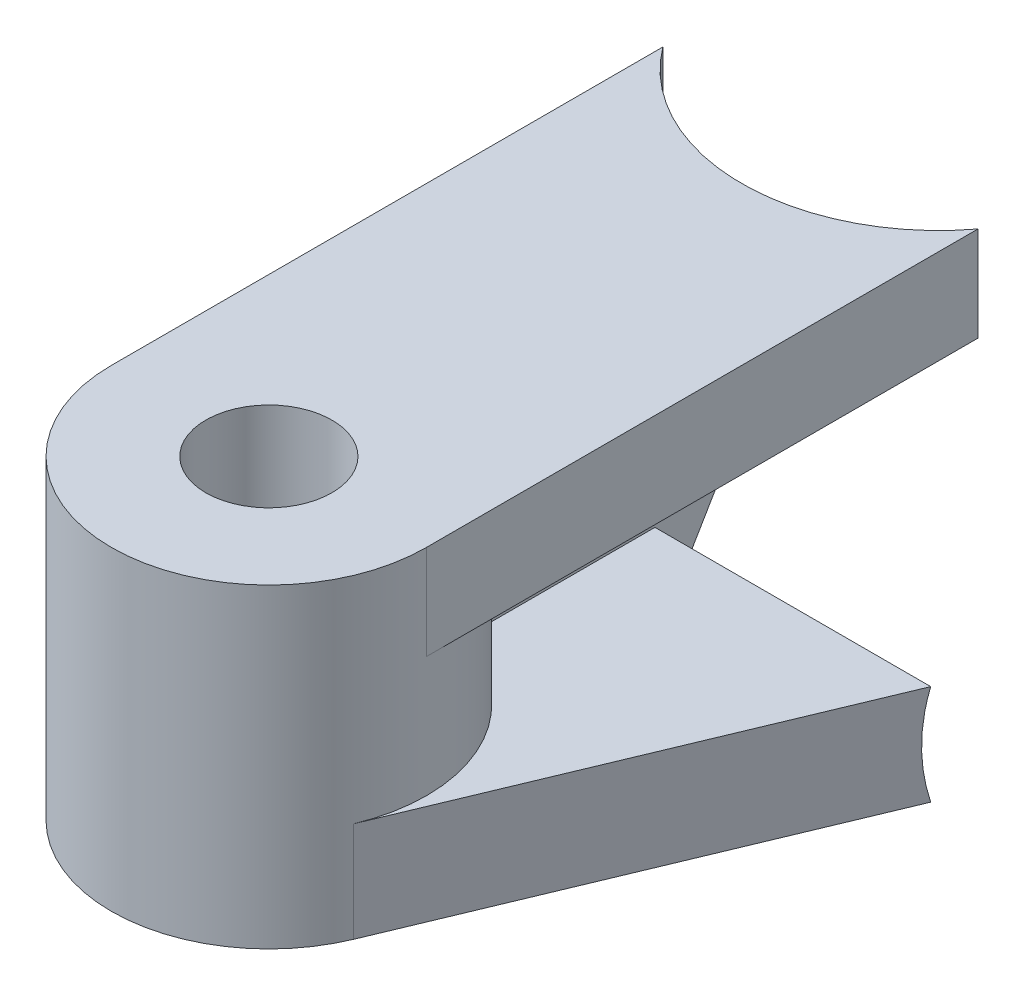
SolidWorks part; units mm, degrees
note: The reader was unsure of these and kept them because the rebuilt part matched: shared geometry of "Sketch1<3>".
ref_plane "Front Plane" through (0, 0, 0) normal (0, 0, 1) x (1, 0, 0)
ref_plane "Top Plane" through (0, 0, 0) normal (0, 1, 0) x (1, 0, 0)
ref_plane "Right Plane" through (0, 0, 0) normal (1, 0, 0) x (0, 0, -1)
sketch "Sketch1" plane through (0, 0, 0) normal (0, 1, 0) x (1, 0, 0)
  line L0 (0, 0) -> (40, 0)
  line L4 (0, 0) -> (10.7692, -25.8462)
  line L5 (29.2308, -25.8462) -> (40, 0)
  line L6 (20, 0) -> (20, -17.1488) construction
  line L7 (10.7692, -25.8462) -> (29.2308, -25.8462) construction
  circle A0 centre (20, -22) radius 4
  circle A1 centre (20, -22) radius 10
  point P7 (10.7978, -25.9141)
  dimension "D2" = 20
  dimension "D3" = 8
  dimension "D1" = 40
  dimension "D4" = 22
extrude "Boss-Extrude1" add sketch "Sketch1" along normal blind 6.35 contours A1 L5 L0 L4
extrude "Boss-Extrude2" add sketch "Sketch1<3>" along normal blind 20 contours A1 A0
sketch "Sketch1<3>" plane through (0, 0, 0) normal (0, 1, 0) x (1, 0, 0) same geometry as "Sketch1"
ref_plane "Plane1" through (0, 10, 0) normal (0, 1, 0) x (1, 0, 0)
sketch "Sketch2" plane through (0, 0, 0) normal (1, 0, 0) x (0, 0, -1)
  line L0 (0, 3.175) -> (21.8325, 3.175) construction
  line L1 (0, 6.35) -> (0, 0) construction
  circle A0 centre (12.0901, 3.175) radius 12.5
  dimension "D1" = 25
extrude "Cut-Extrude1" cut sketch "Sketch2" along normal through all
sketch "Sketch3" plane through (0, 20, 0) normal (0, 1, 0) x (1, 0, 0)
  line L0 (20, 13) -> (20, 20.5) construction
  line L2 (10, -22) -> (10, 13)
  line L3 (10, 13) -> (30, 13)
  line L4 (30, -22) -> (30, 13)
  line L6 (20, 20.5) -> (20, -18)
  circle A1 centre (20, -22) radius 4
  circle A2 centre (20, 20.5) radius 12.5
  circle A3 centre (20, -22) radius 10 construction
  arc A4 (29.2308, -25.8462) -> (10.7692, -25.8462) centre (20, -22) ccw construction
  point P9 (10.0056, -22.3357)
  point P16 (10, -22)
  dimension "D1" = 25
  dimension "D2" = 35
extrude "Boss-Extrude3" add sketch "Sketch3" against normal blind 6
sketch "Sketch4" plane through (0, 14, 0) normal (0, -1, 0) x (1, 0, 0)
  line L0 (20, -8) -> (20, 12) construction
  line L1 (17.5, -8.2526) -> (17.5, 12.3175)
  line L2 (22.5, -8.2526) -> (22.5, 12.3175)
  arc A0 (10, 22) -> (30, 22) centre (20, 22) ccw construction
  arc A1 (30, -13) -> (10, -13) centre (20, -20.5) ccw construction
  arc A2 (17.5, 12.3175) -> (22.5, 12.3175) centre (20, 22) ccw
  arc A3 (22.5, -8.2526) -> (17.5, -8.2526) centre (20, -20.5) ccw
  point P4 (0, 0)
  point P6 (17.1074, 12.4275)
  point P12 (0, 0)
  dimension "D1" = 5
sketch "Sketch5" plane through (0, 0, 0) normal (0, -1, 0) x (1, 0, 0)
  line L0 (22.5, 0) -> (17.5, 0)
  line L1 (22.5, -8.2526) -> (22.5, 12.3175) construction
  line L2 (0, 0) -> (40, 0) construction
  line L3 (17.5, -8.2526) -> (17.5, 12.3175) construction
  line L4 (17.5, 0) -> (17.5, 12.3175)
  line L5 (22.5, 12.3175) -> (22.5, 0)
  arc A0 (17.5, 12.3175) -> (22.5, 12.3175) centre (20, 22) ccw construction
  arc A1 (17.5, 12.3175) -> (22.5, 12.3175) centre (20, 22) ccw
loft "Loft1" add profiles "Sketch5", "Sketch4" connector at (22.5, 0, 12.3175) connector at (22.5, 14, 12.3175)
